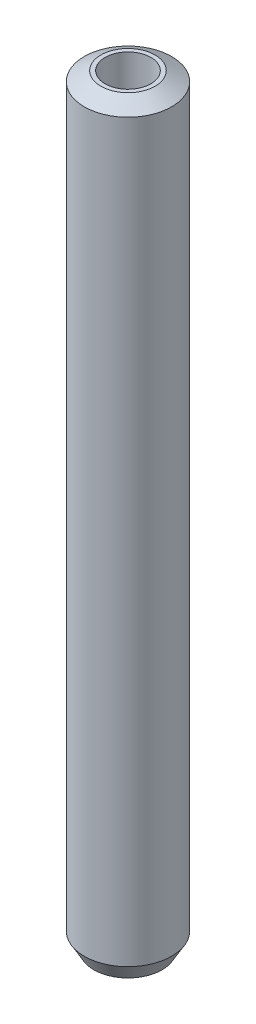
SolidWorks part; units mm, degrees
ref_plane "Front Plane" through (0, 0, 0) normal (0, 0, 1) x (1, 0, 0)
ref_plane "Top Plane" through (0, 0, 0) normal (0, 1, 0) x (1, 0, 0)
ref_plane "Right Plane" through (0, 0, 0) normal (1, 0, 0) x (0, 0, -1)
sketch "Sketch1" plane through (0, 0, 0) normal (0, 1, 0) x (1, 0, 0)
  circle A0 centre (0, 0) radius 10
  dimension "SHAFT_OD" = 20
extrude "Boss-Extrude1" add sketch "Sketch1" along normal blind 174.5247
sketch "Sketch2" plane through (0, 0, 0) normal (0, 1, 0) x (1, 0, 0)
  circle A0 centre (0, 0) radius 5.2459
  dimension "BORE_D" = 10.4917
extrude "Cut-Extrude1" cut sketch "Sketch2" along normal through all
chamfer "Chamfer1" distance 2.1896 angle 60 2 edges at (0, 174.5247, 10) (0, 0, 10) first distance on face at (0, 174.5247, 10) first distance on face at (0, 0, 5.2459)
